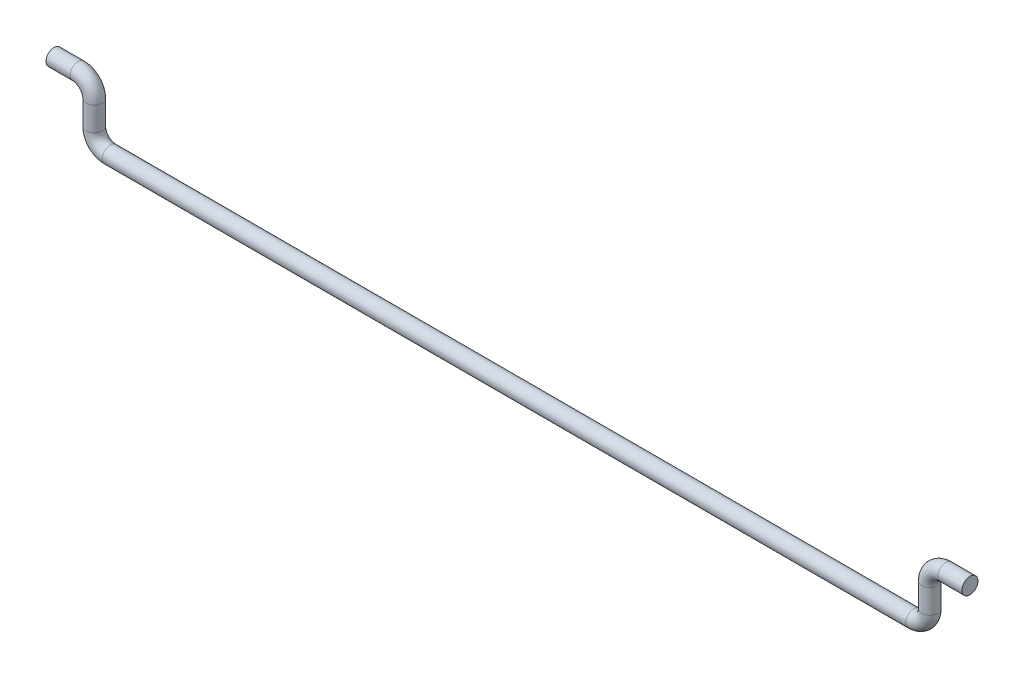
SolidWorks part; units mm, degrees
material "Cast Alloy Steel"
ref_plane "Front Plane" through (0, 0, 0) normal (0, 0, 1) x (1, 0, 0)
ref_plane "Top Plane" through (0, 0, 0) normal (0, 1, 0) x (1, 0, 0)
ref_plane "Right Plane" through (0, 0, 0) normal (1, 0, 0) x (0, 0, -1)
sketch "Sketch1" plane through (0, 0, 0) normal (0, 0, 1) x (1, 0, 0)
  line L0 (0, 0) -> (-100, 0)
  line L1 (-102, 2) -> (-102, 5)
  line L2 (-50, 0) -> (-50, 16.7563) construction
  line L3 (-104, 7) -> (-107, 7)
  line L4 (2, 2) -> (2, 5)
  line L5 (4, 7) -> (7, 7)
  arc A0 (-100, 0) -> (-102, 2) centre (-100, 2) cw
  arc A1 (-102, 5) -> (-104, 7) centre (-104, 5) ccw
  arc A2 (0, 0) -> (2, 2) centre (0, 2) ccw
  arc A3 (2, 5) -> (4, 7) centre (4, 5) cw
  dimension "D2" = 2
  dimension "D1" = 100
  dimension "D3" = 3
  dimension "D4" = 3
ref_plane "Plane1" through (7, 0, 0) normal (1, 0, 0) x (0, 0, -1)
sketch "Sketch3" plane through (7, 0, 0) normal (1, 0, 0) x (0, 0, -1)
  circle A0 centre (0.4304, 7) radius 1
  dimension "D1" = 2
sweep "Sweep2" add profiles "Sketch3" path "Sketch1"
ref_plane "Plane2" through (0, 2, 0) normal (0, 1, 0) x (-1, 0, 0)
sketch "Sketch4" plane through (0, 2, 0) normal (0, 1, 0) x (-1, 0, 0)
  point P0 (102, -0.4304)
